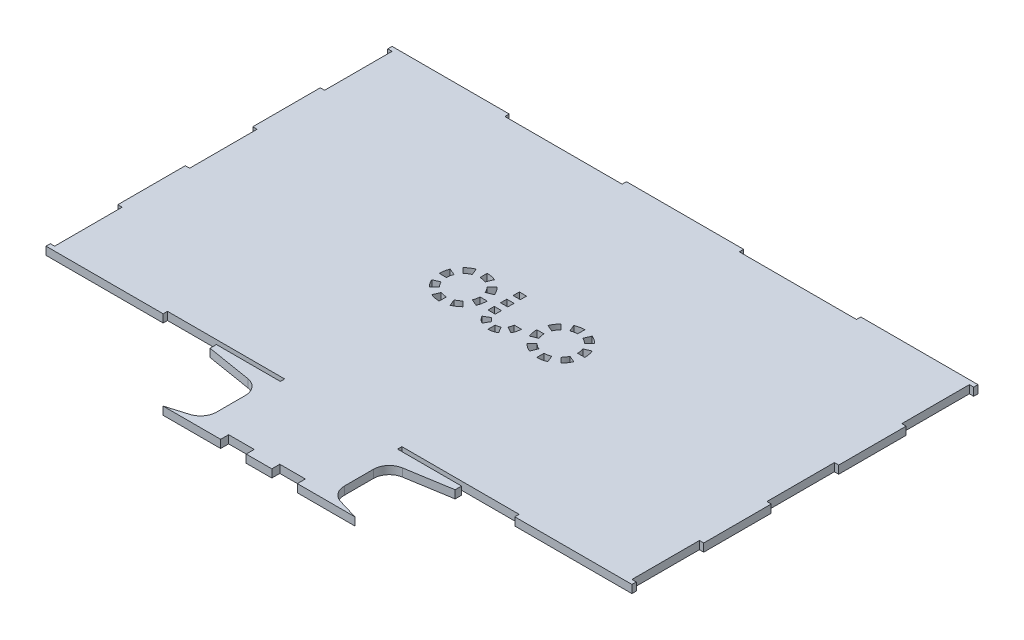
SolidWorks part; units mm, degrees
ref_plane "Front Plane" through (0, 0, 0) normal (0, 0, 1) x (1, 0, 0)
ref_plane "Top Plane" through (0, 0, 0) normal (0, 1, 0) x (1, 0, 0)
ref_plane "Right Plane" through (0, 0, 0) normal (1, 0, 0) x (0, 0, -1)
sketch "Sketch1" plane through (0, 0, 0) normal (0, 1, 0) x (1, 0, 0)
  line L0 (-183.2, 108.2) -> (-109.92, 108.2)
  line L1 (-109.92, 105.5) -> (-36.64, 105.5)
  line L4 (180.5, 105.5) -> (180.5, 63.3)
  line L5 (183.2, 108.2) -> (183.2, 105.5)
  line L8 (183.2, 63.3) -> (183.2, 21.1)
  line L9 (183.2, 108.2) -> (183.2, -108.2) construction
  line L10 (180.5, -105.5) -> (183.2, -105.5)
  line L11 (180.5, 105.5) -> (183.2, 105.5)
  line L13 (180.5, 105.5) -> (180.5, -105.5) construction
  line L14 (180.5, 21.1) -> (180.5, -21.1)
  line L16 (180.5, -63.3) -> (180.5, -105.5)
  line L18 (-180.5, 105.5) -> (-180.5, -105.5) construction
  line L23 (-183.2, 108.2) -> (183.2, 108.2) construction
  line L24 (-36.64, 108.2) -> (36.64, 108.2)
  line L26 (109.92, 108.2) -> (183.2, 108.2)
  line L27 (-109.92, 108.2) -> (-109.92, 105.5)
  line L28 (-36.64, 108.2) -> (-36.64, 105.5)
  line L29 (36.64, 108.2) -> (36.64, 105.5)
  line L30 (109.92, 108.2) -> (109.92, 105.5)
  line L31 (-180.5, 105.5) -> (180.5, 105.5) construction
  line L32 (36.64, 105.5) -> (109.92, 105.5)
  line L33 (-183.2, -108.2) -> (183.2, -108.2) construction
  line L34 (-180.5, -105.5) -> (180.5, -105.5) construction
  line L35 (180.5, -21.1) -> (183.2, -21.1)
  line L36 (109.92, -108.2) -> (183.2, -108.2)
  line L37 (109.92, -108.2) -> (109.92, -105.5)
  line L38 (36.64, -105.5) -> (109.92, -105.5)
  line L39 (36.64, -108.2) -> (36.64, -105.5)
  line L41 (-36.64, -108.2) -> (-36.64, -105.5)
  line L42 (-109.92, -105.5) -> (-36.64, -105.5)
  line L43 (-109.92, -108.2) -> (-109.92, -105.5)
  line L44 (-183.2, -108.2) -> (-109.92, -108.2)
  line L45 (180.5, -63.3) -> (183.2, -63.3)
  line L46 (180.5, 21.1) -> (183.2, 21.1)
  line L47 (180.5, 63.3) -> (183.2, 63.3)
  line L48 (183.2, -21.1) -> (183.2, -63.3)
  line L49 (-183.2, 108.2) -> (-183.2, -108.2) construction
  line L50 (183.2, -105.5) -> (183.2, -108.2)
  line L51 (-40, -126.6956) -> (-40, -144.7597)
  line L52 (-183.2, -105.5) -> (-183.2, -108.2)
  line L53 (-180.5, -105.5) -> (-183.2, -105.5)
  line L54 (-180.5, -63.3) -> (-180.5, -105.5)
  line L55 (-180.5, -63.3) -> (-183.2, -63.3)
  line L56 (-183.2, -21.1) -> (-183.2, -63.3)
  line L57 (-180.5, -21.1) -> (-183.2, -21.1)
  line L58 (-180.5, 21.1) -> (-180.5, -21.1)
  line L59 (-180.5, 21.1) -> (-183.2, 21.1)
  line L60 (-183.2, 63.3) -> (-183.2, 21.1)
  line L61 (-180.5, 63.3) -> (-183.2, 63.3)
  line L62 (-180.5, 105.5) -> (-180.5, 63.3)
  line L63 (-183.2, 108.2) -> (-183.2, 105.5)
  line L64 (-180.5, 105.5) -> (-183.2, 105.5)
  line L67 (40, -126.6956) -> (40, -144.7597)
  line L70 (-40, -158.2) -> (-24, -158.2)
  line L71 (24, -153.2) -> (8, -153.2)
  line L75 (-8, -158.2) -> (8, -158.2)
  line L77 (24, -158.2) -> (40, -158.2)
  line L78 (-24, -158.2) -> (-24, -153.2)
  line L79 (-8, -158.2) -> (-8, -153.2)
  line L80 (8, -158.2) -> (8, -153.2)
  line L81 (24, -158.2) -> (24, -153.2)
  line L82 (-8, -153.2) -> (-24, -153.2)
  line L83 (-36.64, -108.2) -> (-76.64, -108.2)
  line L84 (36.64, -108.2) -> (76.64, -108.2)
  line L85 (-76.64, -108.2) -> (-76.64, -112.2)
  line L86 (-76.64, -112.2) -> (-48.384, -116.8271)
  line L87 (76.64, -108.2) -> (76.64, -112.2)
  line L88 (76.64, -112.2) -> (48.384, -116.8271)
  line L89 (-40, -158.2) -> (-60, -158.2)
  line L90 (40, -158.2) -> (60, -158.2)
  line L92 (-47.1265, -154.338) -> (-60, -158.2)
  line L94 (47.1265, -154.338) -> (60, -158.2)
  line L96 (-10.416, 3.2488) -> (-10.416, 7.1658)
  line L147 (-10.416, 11.0829) -> (-10.416, 15)
  line L148 (-9.0207, -9.7927) -> (-5.1196, -7.5404)
  line L149 (-5.2087, -13.6047) -> (-2.9564, -9.7036)
  line L150 (-0.0014, -10.4954) -> (-0.0014, -15)
  line L151 (5.2059, -13.6047) -> (2.9536, -9.7036)
  line L152 (5.1168, -7.5404) -> (9.0179, -9.7927)
  line L153 (-5.9114, -4.5854) -> (-10.416, -4.5854)
  line L154 (-5.9083, -0.6683) -> (-10.416, -0.6683)
  line L155 (-5.9051, 3.2488) -> (-10.416, 3.2488)
  line L156 (-5.9019, 7.1658) -> (-10.416, 7.1658)
  line L157 (-5.8988, 11.0829) -> (-10.416, 11.0829)
  line L158 (-5.8988, 11.0829) -> (-5.8956, 15)
  line L159 (-5.9051, 3.2488) -> (-5.9019, 7.1658)
  line L160 (-10.416, -4.5854) -> (-10.416, -0.6683)
  line L161 (-5.9114, -4.5854) -> (-5.9083, -0.6683)
  line L162 (-10.416, 15) -> (-5.8956, 15)
  line L163 (10.4131, -4.5854) -> (5.9086, -4.5854)
  line L164 (-24.7875, -13.8582) -> (-26.5096, -9.7007)
  line L165 (-19.9211, -10.6066) -> (-23.1031, -7.4246)
  line L166 (-15.5278, 0) -> (-20.0278, 0)
  line L167 (-16.6696, -5.7403) -> (-20.827, -4.0182)
  line L168 (-19.9211, 10.6066) -> (-23.1031, 7.4246)
  line L169 (-16.6696, 5.7403) -> (-20.827, 4.0182)
  line L170 (-30.5278, 15) -> (-30.5278, 10.5)
  line L171 (-24.7875, 13.8582) -> (-26.5096, 9.7007)
  line L172 (-37.9524, 7.4246) -> (-41.1344, 10.6066)
  line L173 (-34.5459, 9.7007) -> (-36.268, 13.8582)
  line L174 (-41.0278, 0) -> (-45.5278, 0)
  line L175 (-40.2285, 4.0182) -> (-44.3859, 5.7403)
  line L176 (-37.9524, -7.4246) -> (-41.1344, -10.6066)
  line L177 (-40.2285, -4.0182) -> (-44.3859, -5.7403)
  line L178 (-30.5278, -10.5) -> (-30.5278, -15)
  line L179 (-34.5459, -9.7007) -> (-36.268, -13.8582)
  line L180 (24.7875, -13.8582) -> (26.5096, -9.7007)
  line L181 (30.5278, -10.5) -> (30.5278, -15)
  line L182 (34.5459, -9.7007) -> (36.268, -13.8582)
  line L183 (37.9524, -7.4246) -> (41.1344, -10.6066)
  line L184 (40.2285, -4.0182) -> (44.3859, -5.7403)
  line L185 (41.0278, 0) -> (45.5278, 0)
  line L186 (40.2285, 4.0182) -> (44.3859, 5.7403)
  line L187 (37.9524, 7.4246) -> (41.1344, 10.6066)
  line L188 (34.5459, 9.7007) -> (36.268, 13.8582)
  line L189 (30.5278, 15) -> (30.5278, 10.5)
  line L190 (24.7875, 13.8582) -> (26.5096, 9.7007)
  line L191 (19.9211, 10.6066) -> (23.1031, 7.4246)
  line L192 (16.6696, 5.7403) -> (20.827, 4.0182)
  line L193 (15.5278, 0) -> (20.0278, 0)
  line L194 (16.6696, -5.7403) -> (20.827, -4.0182)
  line L195 (19.9211, -10.6066) -> (23.1031, -7.4246)
  arc A0 (-48.384, -116.8271) -> (-40, -126.6956) centre (-50, -126.6956) cw
  arc A1 (40, -126.6956) -> (48.384, -116.8271) centre (50, -126.6956) cw
  arc A2 (-47.1265, -154.338) -> (-40, -144.7597) centre (-50, -144.7597) ccw
  arc A3 (40, -144.7597) -> (47.1265, -154.338) centre (50, -144.7597) ccw
  arc A42 (2.9536, -9.7036) -> (-0.0014, -10.4954) centre (-0.0014, -4.5854) cw
  arc A43 (-2.9564, -9.7036) -> (-5.1196, -7.5404) centre (-0.0014, -4.5854) cw
  arc A44 (-5.2087, -13.6047) -> (-9.0207, -9.7927) centre (-0.0014, -4.5854) cw
  arc A45 (5.2059, -13.6047) -> (-0.0014, -15) centre (-0.0014, -4.5854) cw
  arc A46 (5.9086, -4.5854) -> (5.1168, -7.5404) centre (-0.0014, -4.5854) cw
  arc A47 (10.4131, -4.5854) -> (9.0179, -9.7927) centre (-0.0014, -4.5854) cw
  arc A48 (-26.5096, -9.7007) -> (-23.1031, -7.4246) centre (-30.5278, 0) ccw
  arc A49 (-24.7875, -13.8582) -> (-19.9211, -10.6066) centre (-30.5278, 0) ccw
  arc A50 (-20.827, -4.0182) -> (-20.0278, 0) centre (-30.5278, 0) ccw
  arc A51 (-16.6696, -5.7403) -> (-15.5278, 0) centre (-30.5278, 0) ccw
  arc A52 (-20.827, 4.0182) -> (-23.1031, 7.4246) centre (-30.5278, 0) ccw
  arc A53 (-16.6696, 5.7403) -> (-19.9211, 10.6066) centre (-30.5278, 0) ccw
  arc A54 (-26.5096, 9.7007) -> (-30.5278, 10.5) centre (-30.5278, 0) ccw
  arc A55 (-24.7875, 13.8582) -> (-30.5278, 15) centre (-30.5278, 0) ccw
  arc A56 (-36.268, 13.8582) -> (-41.1344, 10.6066) centre (-30.5278, 0) ccw
  arc A57 (-34.5459, 9.7007) -> (-37.9524, 7.4246) centre (-30.5278, 0) ccw
  arc A58 (-44.3859, 5.7403) -> (-45.5278, 0) centre (-30.5278, 0) ccw
  arc A59 (-40.2285, 4.0182) -> (-41.0278, 0) centre (-30.5278, 0) ccw
  arc A60 (-44.3859, -5.7403) -> (-41.1344, -10.6066) centre (-30.5278, 0) ccw
  arc A61 (-40.2285, -4.0182) -> (-37.9524, -7.4246) centre (-30.5278, 0) ccw
  arc A62 (-36.268, -13.8582) -> (-30.5278, -15) centre (-30.5278, 0) ccw
  arc A63 (-34.5459, -9.7007) -> (-30.5278, -10.5) centre (-30.5278, 0) ccw
  arc A64 (40.2285, 4.0182) -> (41.0278, 0) centre (30.5278, 0) cw
  arc A65 (40.2285, -4.0182) -> (37.9524, -7.4246) centre (30.5278, 0) cw
  arc A66 (34.5459, -9.7007) -> (30.5278, -10.5) centre (30.5278, 0) cw
  arc A67 (26.5096, -9.7007) -> (23.1031, -7.4246) centre (30.5278, 0) cw
  arc A68 (20.827, -4.0182) -> (20.0278, 0) centre (30.5278, 0) cw
  arc A69 (20.827, 4.0182) -> (23.1031, 7.4246) centre (30.5278, 0) cw
  arc A70 (26.5096, 9.7007) -> (30.5278, 10.5) centre (30.5278, 0) cw
  arc A71 (16.6696, -5.7403) -> (15.5278, 0) centre (30.5278, 0) cw
  arc A72 (24.7875, -13.8582) -> (19.9211, -10.6066) centre (30.5278, 0) cw
  arc A73 (36.268, -13.8582) -> (30.5278, -15) centre (30.5278, 0) cw
  arc A74 (44.3859, -5.7403) -> (41.1344, -10.6066) centre (30.5278, 0) cw
  arc A75 (44.3859, 5.7403) -> (45.5278, 0) centre (30.5278, 0) cw
  arc A76 (36.268, 13.8582) -> (41.1344, 10.6066) centre (30.5278, 0) cw
  arc A77 (24.7875, 13.8582) -> (30.5278, 15) centre (30.5278, 0) cw
  arc A78 (34.5459, 9.7007) -> (37.9524, 7.4246) centre (30.5278, 0) cw
  arc A79 (16.6696, 5.7403) -> (19.9211, 10.6066) centre (30.5278, 0) cw
  point P0 (0, 0)
  point P58 (-40, -118.2)
  point P68 (40, -118.2)
  dimension "D2" = 10
  dimension "D3" = 10
  dimension "D6" = 10
  dimension "D7" = 10
  dimension "D1" = 2.7
  dimension "D4" = 40
  dimension "D5" = 40
extrude "Boss-Extrude1" add sketch "Sketch1" along normal blind 5
